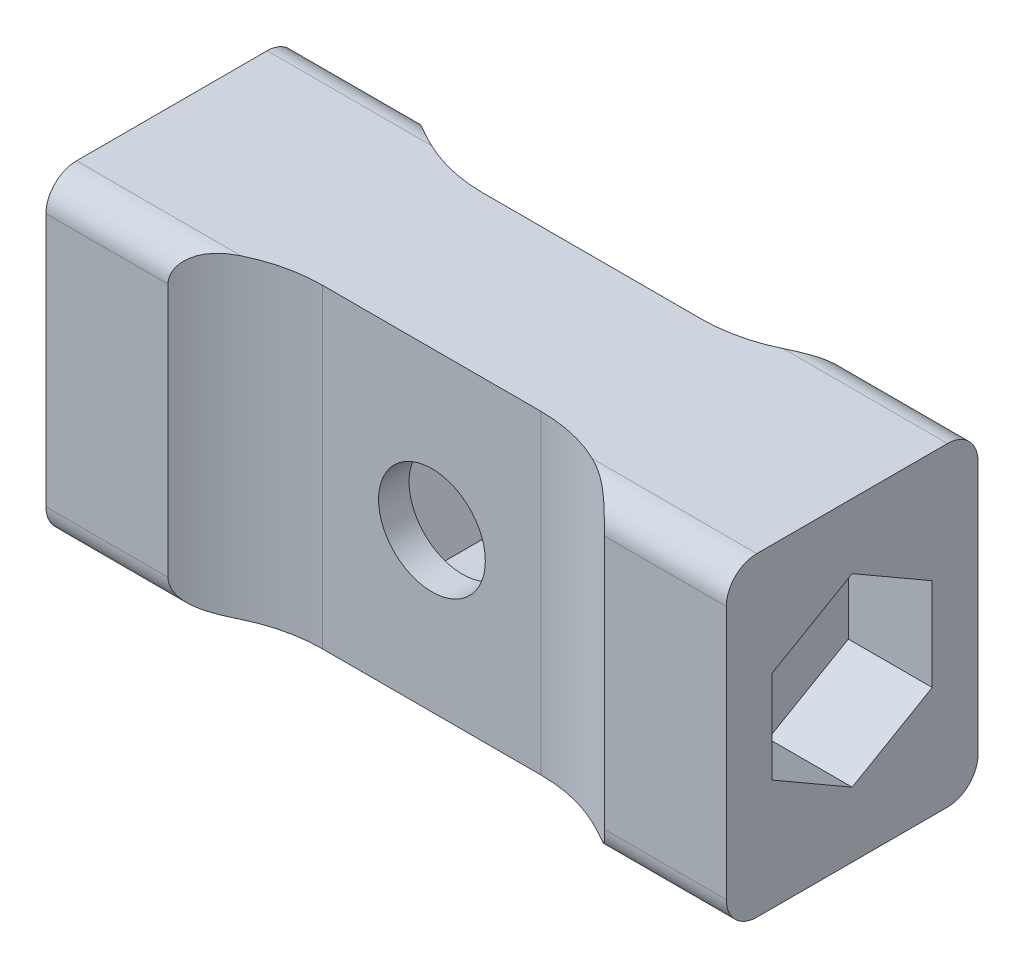
SolidWorks part; units mm, degrees
ref_plane "Alzado" through (0, 0, 0) normal (0, 0, 1) x (1, 0, 0)
ref_plane "Planta" through (0, 0, 0) normal (0, 1, 0) x (1, 0, 0)
ref_plane "Vista lateral" through (0, 0, 0) normal (1, 0, 0) x (0, 0, -1)
sketch "Croquis1" plane through (0, 0, 0) normal (0, 0, 1) x (1, 0, 0)
  line L1 (5.9467, 0) -> (2.9734, 5.15)
  line L2 (2.9734, 5.15) -> (-2.9734, 5.15)
  line L3 (-2.9734, 5.15) -> (-5.9467, 0)
  line L4 (-5.9467, 0) -> (-2.9734, -5.15)
  line L5 (-2.9734, -5.15) -> (2.9734, -5.15)
  line L6 (2.9734, -5.15) -> (5.9467, 0)
  line L7 (-22.3, -10.3237) -> (22.3, -10.3237)
  line L8 (-22.3, -10.3237) -> (-22.3, 10.3237)
  line L9 (-22.3, 10.3237) -> (22.3, 10.3237)
  line L10 (22.3, -10.3237) -> (22.3, 10.3237)
  line L11 (0, 10.3237) -> (0, -10.3237) construction
  line L12 (-22.3, 0) -> (22.3, 0) construction
  circle A0 centre (0, 0) radius 5.15 construction
  dimension "D1" = 10.3
  dimension "D2" = 44.6
extrude "Saliente-Extruir2" add sketch "Croquis1" along normal blind 10.5
sketch "Croquis2" plane through (0, 0, 10.5) normal (0, 0, 1) x (1, 0, 0)
  circle A0 centre (0, 0) radius 7.3663
  circle A1 centre (0, 0) radius 3.5
  dimension "D1" = 7
extrude "Saliente-Extruir3" add sketch "Croquis2" against normal blind 2
sketch "Croquis3" plane through (0, 0, 0) normal (0, 0, -1) x (-1, 0, 0)
  circle A0 centre (0, 0) radius 6.2929
  circle A1 centre (0, 0) radius 3.5
extrude "Saliente-Extruir4" add sketch "Croquis3" against normal blind 2
sketch "Croquis4" plane through (22.3, 0, 0) normal (1, 0, 0) x (0, 0, -1)
  line L0 (-10.5, 0) -> (0, 0) construction
  line L1 (-10.5, -10.3237) -> (-10.5, 10.3237) construction
  line L2 (0, -10.3237) -> (0, 10.3237) construction
  line L3 (-5.25, 10.3237) -> (-5.25, -10.3237) construction
  line L4 (-10.5, 10.3237) -> (0, 10.3237) construction
  line L5 (-10.5, -10.3237) -> (0, -10.3237) construction
  line L7 (-5.25, 6.0622) -> (-10.5, 3.0311)
  line L8 (-10.5, 3.0311) -> (-10.5, -3.0311)
  line L9 (-10.5, -3.0311) -> (-5.25, -6.0622)
  line L10 (-5.25, -6.0622) -> (0, -3.0311)
  line L11 (0, -3.0311) -> (0, 3.0311)
  line L12 (0, 3.0311) -> (-5.25, 6.0622)
  circle A0 centre (-5.25, 0) radius 5.25 construction
  dimension "D1" = 10.5
extrude "Cortar-Extruir1" cut sketch "Croquis4" against normal blind 5.5
sketch "Croquis5" plane through (-22.3, 0, 0) normal (-1, 0, 0) x (0, 0, 1)
  line L0 (0, 0) -> (10.5, 0) construction
  line L1 (10.5, 10.3237) -> (10.5, -10.3237) construction
  line L2 (5.25, 10.3237) -> (5.25, -10.3237) construction
  line L3 (10.5, 10.3237) -> (0, 10.3237) construction
  line L4 (10.5, -10.3237) -> (0, -10.3237) construction
  line L6 (5.25, 6.0622) -> (0, 3.0311)
  line L7 (0, 3.0311) -> (0, -3.0311)
  line L8 (0, -3.0311) -> (5.25, -6.0622)
  line L9 (5.25, -6.0622) -> (10.5, -3.0311)
  line L10 (10.5, -3.0311) -> (10.5, 3.0311)
  line L11 (10.5, 3.0311) -> (5.25, 6.0622)
  circle A0 centre (5.25, 0) radius 5.25 construction
  dimension "D1" = 10.5
extrude "Cortar-Extruir2" cut sketch "Croquis5" against normal blind 5.5
sketch "Croquis6" plane through (0, 0, 0) normal (0, 0, -1) x (-1, 0, 0)
  line L0 (22.3, -10.3237) -> (-22.3, -10.3237) construction
  line L1 (-22.3, 10.3237) -> (-14.3, 10.3237)
  line L2 (-22.3, 10.3237) -> (-22.3, -10.3237)
  line L3 (-22.3, -10.3237) -> (-14.3, -10.3237)
  line L4 (-14.3, 10.3237) -> (-14.3, -10.3237)
  line L5 (-22.3, 10.3237) -> (22.3, 10.3237) construction
  line L6 (22.3, 10.3237) -> (14.3, 10.3237)
  line L7 (22.3, 10.3237) -> (22.3, -10.3237)
  line L8 (22.3, -10.3237) -> (14.3, -10.3237)
  line L9 (14.3, 10.3237) -> (14.3, -10.3237)
  line L10 (22.3, 10.3237) -> (22.3, 3.0311) construction
  dimension "D1" = 8
  dimension "D2" = 8
extrude "Saliente-Extruir5" add sketch "Croquis6" along normal blind 3
sketch "Croquis7" plane through (0, 0, 10.5) normal (0, 0, 1) x (1, 0, 0)
  line L0 (-22.3, -10.3237) -> (22.3, -10.3237) construction
  line L1 (-22.3, 10.3237) -> (-14.3, 10.3237)
  line L2 (-22.3, 10.3237) -> (-22.3, -10.3237)
  line L3 (-22.3, -10.3237) -> (-14.3, -10.3237)
  line L4 (-14.3, 10.3237) -> (-14.3, -10.3237)
  line L6 (22.3, 10.3237) -> (14.3, 10.3237)
  line L7 (22.3, 10.3237) -> (22.3, -10.3237)
  line L8 (22.3, -10.3237) -> (14.3, -10.3237)
  line L9 (14.3, 10.3237) -> (14.3, -10.3237)
  dimension "D1" = 8
  dimension "D2" = 8
extrude "Saliente-Extruir6" add sketch "Croquis7" along normal blind 3
fillet "Redondeo1" radius 10 4 edges at (-14.3, 0, 10.5) (14.3, 0, 10.5) (14.3, 0, 0) (-14.3, 0, 0)
fillet "Redondeo2" radius 2 7 edges at (18.3, -10.3237, 13.5) (18.3, 10.3237, 13.5) (18.3, 10.3237, -3) (-18.3, 10.3237, -3) (-18.3, 10.3237, 13.5) (18.3, -10.3237, -3) (-18.3, -10.3237, 13.5)
